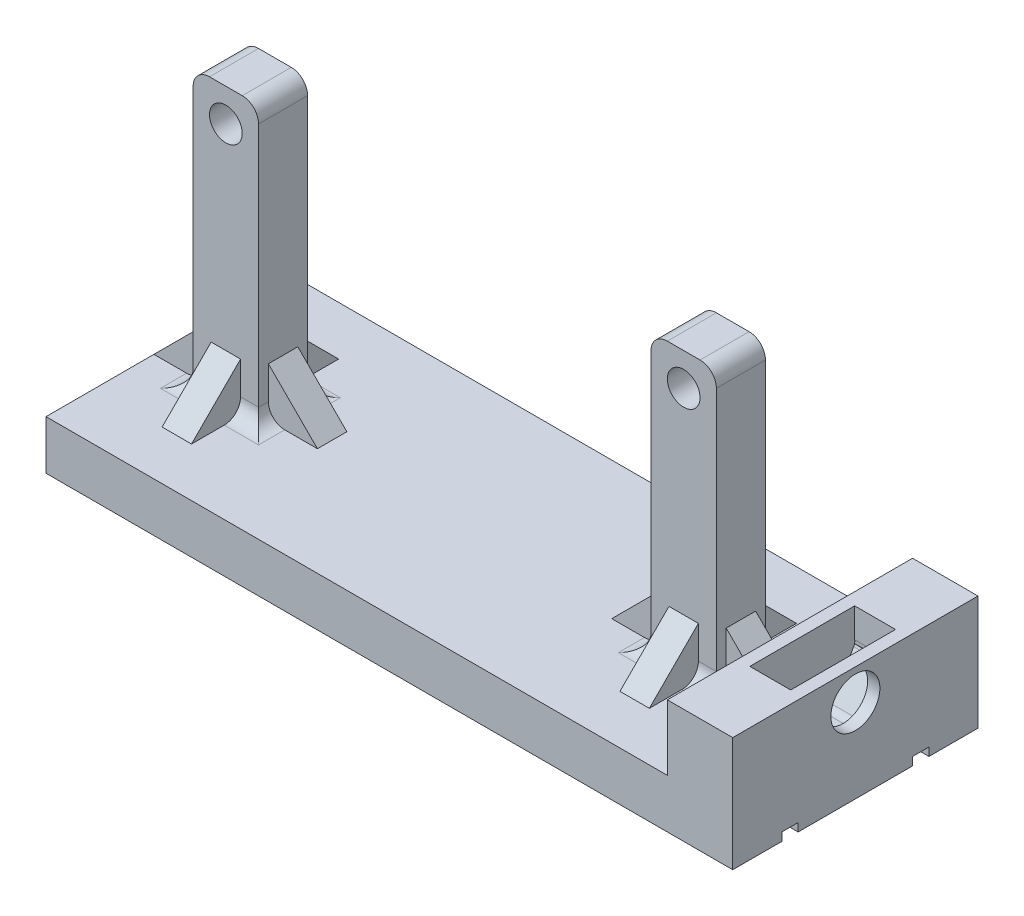
SolidWorks part; units mm, degrees
ref_plane "Alzado" through (0, 0, 0) normal (0, 0, 1) x (1, 0, 0)
ref_plane "Planta" through (0, 0, 0) normal (0, 1, 0) x (1, 0, 0)
ref_plane "Vista lateral" through (0, 0, 0) normal (1, 0, 0) x (0, 0, -1)
sketch "Croquis1" plane through (0, 0, 0) normal (0, 0, 1) x (1, 0, 0)
  line L0 (0, 0) -> (38, 0)
  line L1 (38, 0) -> (38, 3)
  line L2 (38, 3) -> (35, 3)
  line L3 (35, 3) -> (35, 20)
  line L4 (35, 20) -> (31, 20)
  line L5 (31, 20) -> (31, 3)
  line L6 (31, 3) -> (7, 3)
  line L7 (7, 3) -> (7, 20)
  line L8 (7, 20) -> (3, 20)
  line L9 (3, 20) -> (3, 3)
  line L10 (0, 0) -> (0, 3)
  line L11 (0, 3) -> (3, 3)
  circle A0 centre (5, 18) radius 1
  circle A1 centre (33, 18) radius 1
  point P19 (5, 20)
  point P21 (33, 20)
  dimension "D1" = 2
  dimension "D2" = 28
  dimension "D3" = 15
  dimension "D4" = 2
  dimension "D5" = 3
  dimension "D6" = 4
  dimension "D7" = 3
extrude "Saliente-Extruir1" add sketch "Croquis1" along normal mid plane 3
sketch "Croquis2" plane through (0, 0, 1.5) normal (0, 0, 1) x (1, 0, 0)
  line L1 (0, 3) -> (38, 3)
  line L2 (0, 3) -> (0, 0)
  line L3 (0, 0) -> (38, 0)
  line L4 (38, 3) -> (38, 0)
extrude "Saliente-Extruir2" add sketch "Croquis2" along normal blind 6
sketch "Croquis3" plane through (0, 0, -1.5) normal (0, 0, -1) x (-1, 0, 0)
  line L1 (-38, 3) -> (0, 3)
  line L2 (-38, 3) -> (-38, 0)
  line L3 (-38, 0) -> (0, 0)
  line L4 (0, 3) -> (0, 0)
extrude "Saliente-Extruir3" add sketch "Croquis3" along normal blind 6
fillet "Redondeo1" radius 1 4 edges at (35, 20, 0) (31, 20, 0) (7, 20, 0) (3, 20, 0)
sketch "Croquis4" plane through (0, 0, 0) normal (0, 0, 1) x (1, 0, 0)
  line L3 (35, 6) -> (38, 3)
  line L4 (35, 3) -> (35, 19) construction
  dimension "D2" = 3
  dimension "D4" = 3
rib "Nervio1" sketch "Croquis4" sketch "Croquis4" thickness 1.8 extrusion direction parallel to sketch draft on no parameters "D1"=1.8
sketch "Croquis5" plane through (0, 0, 0) normal (0, 0, 1) x (1, 0, 0)
  line L0 (31, 6) -> (28, 3)
  line L1 (31, 19) -> (31, 3) construction
  line L2 (38, 3) -> (0, 3) construction
  dimension "D1" = 3
  dimension "D2" = 3
rib "Nervio5" sketch "Croquis5" sketch "Croquis5" thickness 1.8 extrusion direction parallel to sketch draft on no parameters "D1"=1.8
ref_plane "Plano2" through (33, 0, 0) normal (1, 0, 0) x (0, 0, -1)
sketch "Croquis6" plane through (33, 0, 0) normal (1, 0, 0) x (0, 0, -1)
  line L0 (1.5, 6) -> (4.5, 3)
  line L1 (1.5, 3) -> (1.5, 19) construction
  line L2 (0.9, 3) -> (7.5, 3) construction
  dimension "D1" = 3
  dimension "D2" = 3
rib "Nervio6" sketch "Croquis6" sketch "Croquis6" thickness 1.8 extrusion direction parallel to sketch draft on no parameters "D1"=1.8
sketch "Croquis7" plane through (33, 0, 0) normal (1, 0, 0) x (0, 0, -1)
  line L0 (-1.5, 6) -> (-4.5, 3)
  line L1 (-1.5, 3) -> (-1.5, 19) construction
  line L2 (-7.5, 3) -> (-0.9, 3) construction
  dimension "D1" = 3
  dimension "D2" = 3
rib "Nervio7" sketch "Croquis7" sketch "Croquis7" thickness 1.8 extrusion direction parallel to sketch draft on no parameters "D1"=1.8
ref_plane "Plano1" through (19, 0, 0) normal (-1, 0, 0) x (0, 0, 1)
mirror "Simetría3" about plane through (19, 0, 0) normal (-1, 0, 0) of "Nervio1", "Nervio7", "Nervio6", "Nervio5"
fillet "Redondeo2" radius 1 16 edges at (31.55, 3, 1.5) (31, 3, 1.2) (34.45, 3, 1.5) (35, 3, 1.2) (35, 3, -1.2) (34.45, 3, -1.5) (31, 3, -1.2) (31.55, 3, -1.5) (3, 3, -1.2) (3.55, 3, -1.5) (6.45, 3, -1.5) (7, 3, -1.2) (7, 3, 1.2) (6.45, 3, 1.5) (3, 3, 1.2) (3.55, 3, 1.5)
sketch "Croquis8" plane through (0, 0, 0) normal (0, -1, 0) x (1, 0, 0)
  line L0 (0, 7.5) -> (0, -7.5) construction
  line L1 (0, 4.5) -> (38, 4.5)
  line L2 (0, 4.5) -> (0, 3.5)
  line L3 (0, 3.5) -> (38, 3.5)
  line L4 (38, 4.5) -> (38, 3.5)
  line L5 (38, 7.5) -> (38, -7.5) construction
  line L6 (0, 7.5) -> (38, 7.5) construction
  line L7 (0, -3.5) -> (38.2491, -3.5)
  line L8 (0, -3.5) -> (0, -4.5)
  line L9 (0, -4.5) -> (38.2491, -4.5)
  line L10 (38.2491, -3.5) -> (38.2491, -4.5)
  line L11 (38, -7.5) -> (0, -7.5) construction
  dimension "D1" = 3
  dimension "D2" = 3
  dimension "D3" = 1
  dimension "D4" = 1
extrude "Cortar-Extruir1" cut sketch "Croquis8" against normal blind 0.5
sketch "Croquis10" plane through (0, 3, 0) normal (0, 1, 0) x (1, 0, 0)
  line L1 (42, 7.5) -> (38, 7.5)
  line L2 (42, 7.5) -> (42, -7.5)
  line L3 (42, -7.5) -> (38, -7.5)
  line L4 (38, 7.5) -> (38, -7.5)
  line L6 (38, -7.5) -> (0, -7.5) construction
  line L7 (0, 7.5) -> (38, 7.5) construction
  dimension "D1" = 4
extrude "Saliente-Extruir5" add sketch "Croquis10" against normal up to surface (3 mm away) and the other way blind 4 from surface up to face at (19, 0, 0) starting at face at (19, 3, 0)
sketch "Croquis11" plane through (38, 0, 0) normal (-1, 0, 0) x (0, 0, 1)
  line L0 (7.5, 0) -> (-7.5, 0) construction
  line L1 (1.6454, 2.27) -> (3.2909, 5.12)
  line L2 (3.2909, 5.12) -> (1.6454, 7.97)
  line L3 (1.6454, 7.97) -> (-1.6454, 7.97)
  line L4 (-1.6454, 7.97) -> (-3.2909, 5.12)
  line L5 (-3.2909, 5.12) -> (-1.6454, 2.27)
  line L6 (-1.6454, 2.27) -> (1.6454, 2.27)
  circle A0 centre (0, 5.12) radius 2.85 construction
  circle A1 centre (0, 5.12) radius 1.5
  dimension "D1" = 5.7
  dimension "D3" = 3
  dimension "D2" = 5.12
extrude "Cortar-Extruir2" cut sketch "Croquis11" along normal mid plane 2.5 from offset 2 contours L4 L5 L6 L1 L2 L3 offset against normal yes
fillet "Redondeo5" radius 0.5 4 edges at (40, 5.12, -3.2909) (40, 2.27, -1.6454) (40, 5.12, 3.2909) (40, 2.27, 1.6454)
sketch "Croquis13" plane through (0, 0, 0) normal (0, -1, 0) x (1, 0, 0)
  line L0 (42, 7.5) -> (42, -7.5) construction
  line L1 (38, 4.5) -> (42, 4.5)
  line L2 (38, 4.5) -> (38, 3.5)
  line L3 (38, 3.5) -> (42, 3.5)
  line L4 (42, 4.5) -> (42, 3.5)
  line L6 (38, -3.5) -> (42, -3.5)
  line L7 (38, -3.5) -> (38, -4.5)
  line L8 (38, -4.5) -> (42, -4.5)
  line L9 (42, -3.5) -> (42, -4.5)
  dimension "D1" = 1
  dimension "D2" = 1
extrude "Cortar-Extruir4" cut sketch "Croquis13" against normal blind 0.5
sketch "Croquis14" plane through (0, 7, 0) normal (0, 1, 0) x (1, 0, 0)
  line L0 (38.75, 1.3568) -> (38.75, -1.3568) construction
  line L1 (38.75, 3.2055) -> (41.25, 3.2055)
  line L2 (38.75, 3.2055) -> (38.75, -3.2055)
  line L3 (38.75, -3.2055) -> (41.25, -3.2055)
  line L4 (41.25, 3.2055) -> (41.25, -3.2055)
  line L5 (41.25, 1.3568) -> (41.25, -1.3568) construction
  line L6 (41.25, -2.2055) -> (38.75, -2.2055) construction
  line L7 (38.75, 2.2055) -> (41.25, 2.2055) construction
  dimension "D1" = 1
  dimension "D2" = 1
extrude "Cortar-Extruir5" cut sketch "Croquis14" against normal blind 2
extrude "Cortar-Extruir6" cut sketch "Croquis11<3>" against normal blind 4 from surface contours A1 starting at face at (41.25, 4.605, 0)
sketch "Croquis11<3>" plane through (38, 0, 0) normal (-1, 0, 0) x (0, 0, 1) same geometry as "Croquis11"
equation "\"h\"= 15"
equation "\"D3@Croquis1\"=\"h\""
